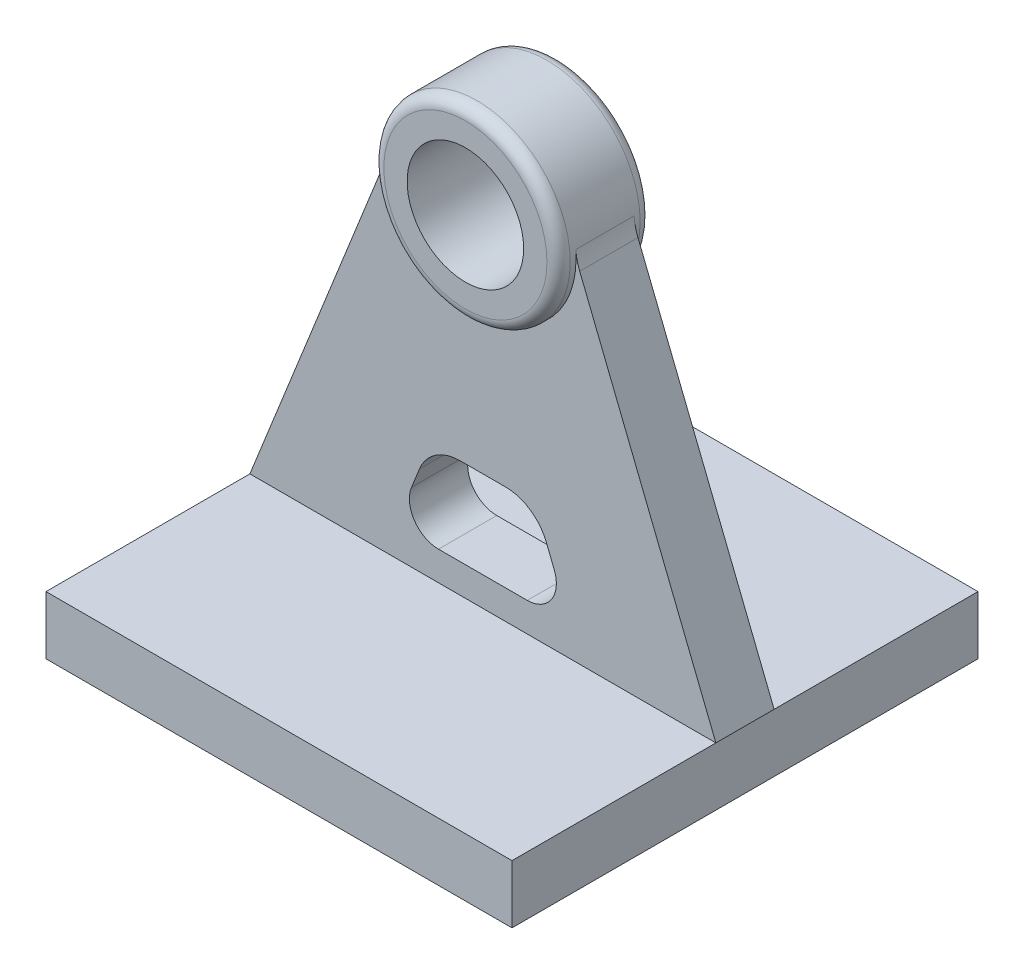
SolidWorks part; units mm, degrees
material "AISI 304"
ref_plane "Front Plane" through (0, 0, 0) normal (0, 0, 1) x (1, 0, 0)
ref_plane "Top Plane" through (0, 0, 0) normal (0, 1, 0) x (1, 0, 0)
ref_plane "Right Plane" through (0, 0, 0) normal (1, 0, 0) x (0, 0, -1)
sketch "Sketch1" plane through (0, 0, 0) normal (0, 1, 0) x (1, 0, 0)
  line L1 (-25.4, -25.4) -> (25.4, -25.4)
  line L2 (-25.4, -25.4) -> (-25.4, 25.4)
  line L3 (-25.4, 25.4) -> (25.4, 25.4)
  line L4 (25.4, -25.4) -> (25.4, 25.4)
  line L5 (-25.4, -25.4) -> (25.4, 25.4) construction
  line L6 (-25.4, 25.4) -> (25.4, -25.4) construction
  point P0 (0, 0)
  dimension "D1" = 50.8
  dimension "D2" = 50.8
extrude "Boss-Extrude1" add sketch "Sketch1" along normal blind 6.35
sketch "Sketch2" plane through (0, 0, 0) normal (0, 0, 1) x (1, 0, 0)
  line L0 (-25.4, 6.35) -> (25.4, 6.35) construction
  circle A0 centre (0, 44.45) radius 10.16
  circle A1 centre (0, 44.45) radius 6.35
  dimension "D1" = 38.1
extrude "Boss-Extrude2" add sketch "Sketch2" along normal mid plane 10.16 separate body
sketch "Sketch4" plane through (0, 0, 0) normal (0, 0, 1) x (1, 0, 0)
  line L0 (-10.16, 44.45) -> (-25.4, 6.35)
  line L1 (-25.4, 6.35) -> (25.4, 6.35) construction
  line L2 (-25.4, 6.35) -> (-25.4, 0) construction
  line L3 (-25.4, 6.35) -> (25.4, 6.35)
  line L4 (25.4, 6.35) -> (10.16, 44.45)
  circle A0 centre (0, 44.45) radius 10.16 construction
  arc A1 (-10.16, 44.45) -> (10.16, 44.45) centre (0, 44.45) ccw
extrude "Boss-Extrude3" add sketch "Sketch4" along normal mid plane 6.35
fillet "Fillet2" radius 1.27 2 edges at (10.16, 44.45, -5.08) (10.16, 44.45, 5.08)
fillet "Fillet3" radius 6.35 2 edges at (-10.16, 44.45, 0) (10.16, 44.45, 0)
ref_point "Point2"
sketch "Sketch6" plane through (0, 0, 3.175) normal (0, 0, 1) x (1, 0, 0)
  line L0 (0, 44.45) -> (0, 19.05) construction
  line L1 (-2.4906, 19.05) -> (2.4906, 19.05)
  line L2 (6.9125, 16.0562) -> (7.7833, 13.8792)
  line L3 (4.8354, 9.525) -> (-4.8354, 9.525)
  line L4 (-25.4, 6.35) -> (25.4, 6.35) construction
  line L5 (25.4, 6.35) -> (10.5577, 43.4557) construction
  line L6 (-6.9125, 16.0562) -> (-7.7833, 13.8792)
  line L7 (0, 9.525) -> (0, 0) construction
  arc A0 (2.4906, 19.05) -> (6.9125, 16.0562) centre (2.4906, 14.2875) cw
  arc A1 (7.7833, 13.8792) -> (4.8354, 9.525) centre (4.8354, 12.7) cw
  arc A2 (-7.7833, 13.8792) -> (-4.8354, 9.525) centre (-4.8354, 12.7) ccw
  arc A3 (-2.4906, 19.05) -> (-6.9125, 16.0562) centre (-2.4906, 14.2875) ccw
  point P16 (9.525, 9.525)
  point P18 (0, 9.525)
  point P22 (0, 19.05)
  dimension "D4" = 4.7625
  dimension "D5" = 3.175
  dimension "D1" = 3.175
  dimension "D2" = 9.525
  dimension "D3" = 9.525
extrude "Cut-Extrude1" cut sketch "Sketch6" against normal up to surface (6.35 mm away) contours A2 L3 A1 L2 A0 L1 A3 L6 up to face at (0, 29.8597, -3.175)
